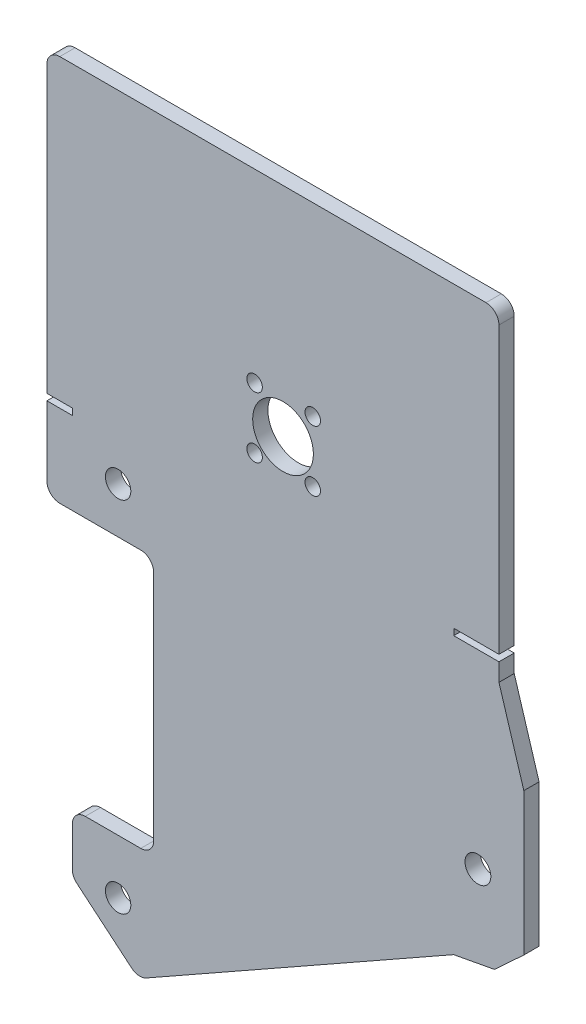
SolidWorks part; units mm, degrees
ref_plane "Front Plane" through (0, 0, 0) normal (0, 0, 1) x (1, 0, 0)
ref_plane "Top Plane" through (0, 0, 0) normal (0, 1, 0) x (1, 0, 0)
ref_plane "Right Plane" through (0, 0, 0) normal (1, 0, 0) x (0, 0, -1)
sketch "Sketch1" plane through (0, 0, 0) normal (0, 0, 1) x (1, 0, 0)
  line L0 (0, 0) -> (88.9, 0)
  line L1 (88.9, 0) -> (88.9, -3.5)
  line L2 (88.9, -3.5) -> (93.7917, -19.5)
  line L3 (93.7917, -19.5) -> (93.7917, -47.5)
  line L4 (0, 0) -> (0, -16.2)
  line L5 (0, -16.2) -> (21, -16.2)
  line L6 (21, -16.2) -> (21, -67)
  line L7 (21, -67) -> (5, -67)
  line L8 (5, -67) -> (5, -78.5)
  line L9 (5, -78.5) -> (18, -89.4083)
  line L10 (18, -89.4083) -> (80, -54.3304)
  line L11 (80, -54.3304) -> (88, -52.8477)
  line L12 (88, -52.8477) -> (93.7917, -47.5)
  dimension "D1" = 88.9
  dimension "D2" = 3.5
  dimension "D3" = 163
  dimension "D4" = 16
  dimension "D5" = 28
  dimension "D6" = 89.4083
  dimension "D7" = 21
  dimension "D8" = 50.8
  dimension "D9" = 16
  dimension "D10" = 11.5
  dimension "D11" = 130
  dimension "D12" = 13
  dimension "D13" = 110.5
  dimension "D14" = 62
  dimension "D15" = 8
  dimension "D16" = 161
extrude "Boss-Extrude1" add sketch "Sketch1" along normal blind 3
sketch "Sketch2" plane through (0, 0, 0) normal (0, 1, 0) x (1, 0, 0)
  line L0 (45.8978, 14) -> (40.3978, 14) construction
  line L1 (0, -3) -> (88.9, -3)
  line L2 (0, -3) -> (0, 54)
  line L3 (0, 54) -> (88.9, 54)
  line L4 (88.9, -3) -> (88.9, 54)
  circle A0 centre (40.3978, 8.5) radius 1.5
  circle A1 centre (40.3978, 20) radius 1.5
  circle A2 centre (51.8978, 8.5) radius 1.5
  circle A3 centre (51.8978, 20) radius 1.5
  ellipse E0 centre (45.8978, 14) end of major axis (45.8978, 8) minor radius 5.5
  dimension "D9" = 3
  dimension "D10" = 3
  dimension "D11" = 3
  dimension "D12" = 3
  dimension "D1" = 88.9
  dimension "D2" = 57
  dimension "D3" = 45.8978
  dimension "D4" = 5.5
  dimension "D5" = 11.5
  dimension "D6" = 23
  dimension "D7" = 11.5
  dimension "D8" = 17
  dimension "D13" = 12
  dimension "D14" = 11
extrude "Boss-Extrude2" add sketch "Sketch2" along normal blind 3
ref_plane "Plane1" through (85.9, 0, 0) normal (1, 0, 0) x (0, 0, -1)
sketch "Sketch3" plane through (85.9, 0, 0) normal (1, 0, 0) x (0, 0, -1)
  line L0 (11.5, 0) -> (0, 0)
  line L1 (0, 0) -> (54, 0) construction
  line L2 (0, 0) -> (0, -11.5)
  line L3 (0, -19.5) -> (0, -3.5) construction
  line L4 (0, -11.5) -> (11.5, 0)
  dimension "D1" = 11.5
  dimension "D2" = 11.5
extrude "Boss-Extrude3" add sketch "Sketch3" against normal blind 84.5
sketch "Sketch4" plane through (0, 0, 0) normal (0, 0, -1) x (-1, 0, 0)
  line L0 (-1.4, -11.5) -> (-85.9, -11.5) construction
  line L1 (-81.4, -11.5) -> (-6.4, -11.5)
  line L2 (-81.4, -11.5) -> (-81.4, 0)
  line L3 (-81.4, 0) -> (-6.4, 0)
  line L4 (-6.4, -11.5) -> (-6.4, 0)
  line L5 (-50.8976, 0) -> (-85.9, 0) construction
  line L6 (-85.9, 13.7659) -> (-85.9, -13.7659) construction
  dimension "D1" = 75
  dimension "D2" = 4.5
extrude "Cut-Extrude2" cut sketch "Sketch4" along normal blind 84.5
sketch "Sketch6" plane through (0, 0, 3) normal (0, 0, 1) x (1, 0, 0)
  line L0 (0, 3) -> (0, -16.2) construction
  line L1 (0, 3) -> (88.9, 3) construction
  circle A0 centre (14, -77.66) radius 2.5
  circle A1 centre (84.763, -37.386) radius 2.54
  circle A2 centre (14, -7.16) radius 2.5
  dimension "D1" = 5
  dimension "D2" = 5
  dimension "D3" = 5.08
  dimension "D4" = 14
  dimension "D5" = 10.16
  dimension "D6" = 70.5
  dimension "D7" = 14
  dimension "D8" = 40.386
  dimension "D9" = 70.763
extrude "Cut-Extrude3" cut sketch "Sketch6" against normal blind 84.5
sketch "Sketch7" plane through (0, 0, 0) normal (0, -1, 0) x (1, 0, 0)
  line L1 (88.9, -54) -> (0, -54)
  line L2 (88.9, -54) -> (88.9, 0)
  line L3 (88.9, 0) -> (0, 0)
  line L4 (0, -54) -> (0, 0)
extrude "Cut-Extrude4" cut sketch "Sketch7" against normal through all both and the other way through all
sketch "Sketch8" plane through (0, 0, 0) normal (0, 0, -1) x (-1, 0, 0)
  line L0 (-88.9, 3) -> (0, 3) construction
  line L1 (-88.9, 3) -> (0, 3)
  line L2 (-88.9, 3) -> (-88.9, 59.896)
  line L3 (-88.9, 59.896) -> (0, 59.896)
  line L4 (0, 3) -> (0, 59.896)
  line L5 (-46.4351, 17.1224) -> (-40.4661, 17.1224) construction
  line L6 (-14, -77.66) -> (-84.763, -77.66) construction
  line L7 (-84.763, -77.66) -> (-84.763, -37.386) construction
  line L8 (-49.3815, -77.66) -> (-49.3815, 51.3441) construction
  line L9 (-58.3815, 3) -> (-58.3815, 17.1224) construction
  line L10 (-58.3815, 17.1224) -> (-46.4351, 17.1224) construction
  circle A0 centre (-46.4351, 17.1224) radius 5.969
  circle A1 centre (-40.8471, 23.4724) radius 1.524
  circle A2 centre (-40.8471, 11.5344) radius 1.524
  circle A3 centre (-52.2771, 23.4724) radius 1.524
  circle A4 centre (-52.2771, 11.5344) radius 1.524
  dimension "D8" = 11.938
  dimension "D9" = 3.048
  dimension "D10" = 3.048
  dimension "D11" = 3.048
  dimension "D12" = 3.048
  dimension "D1" = 56.896
  dimension "D2" = 88.9
  dimension "D3" = 14.1224
  dimension "D4" = 5.588
  dimension "D5" = 2.9464
  dimension "D6" = 11.938
  dimension "D7" = 5.588
  dimension "D14" = 11.43
extrude "Boss-Extrude4" add sketch "Sketch8" against normal up to surface (3 mm away) up to face at (16.5, -77.66, 3)
sketch "Sketch10" plane through (0, 0, 0) normal (0, 0, -1) x (-1, 0, 0)
  line L0 (-88.9, -3.5) -> (-88.9, 59.896) construction
  line L1 (0, 0) -> (-5.08, 0)
  line L2 (0, 0) -> (0, 1.27)
  line L3 (0, 1.27) -> (-5.08, 1.27)
  line L4 (-5.08, 0) -> (-5.08, 1.27)
  line L5 (-80.01, 0) -> (-88.9, 0)
  line L6 (-80.01, 0) -> (-80.01, 1.27)
  line L7 (-80.01, 1.27) -> (-88.9, 1.27)
  line L8 (-88.9, 0) -> (-88.9, 1.27)
  dimension "D1" = 5.08
  dimension "D2" = 1.27
  dimension "D3" = 8.89
  dimension "D4" = 1.27
extrude "Cut-Extrude5" cut sketch "Sketch10" against normal blind 10
fillet "Fillet1" radius 2.54 8 edges at (18, -89.4083, 1.5) (21, -16.2, 1.5) (21, -67, 1.5) (5, -67, 1.5) (0, -16.2, 1.5) (0, 59.896, 1.5) (88.9, 59.896, 1.5) (5, -78.5, 1.5)
